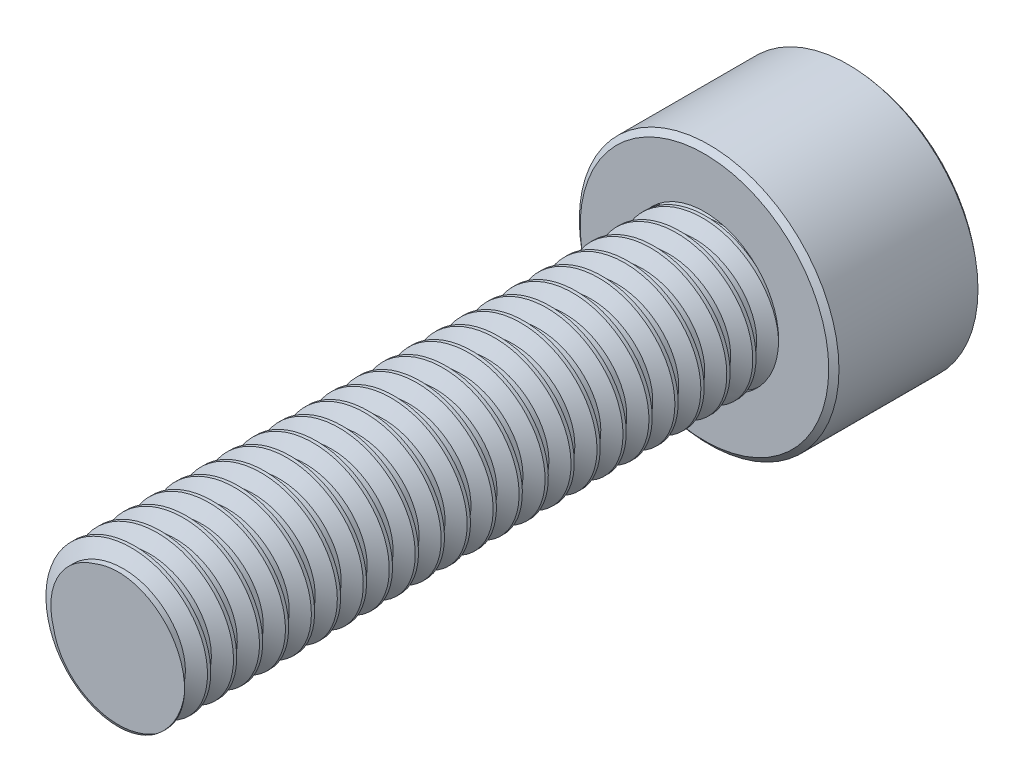
SolidWorks part; units mm, degrees
ref_plane "Front Plane" through (0, 0, 0) normal (0, 0, 1) x (1, 0, 0)
ref_plane "Top Plane" through (0, 0, 0) normal (0, 1, 0) x (1, 0, 0)
ref_plane "Right Plane" through (0, 0, 0) normal (1, 0, 0) x (0, 0, -1)
sketch "Sketch3" plane through (0, 0, 0) normal (0, 0, 1) x (1, 0, 0)
  circle A0 centre (0, 0) radius 2
extrude "Boss-Extrude2" add sketch "Sketch3" along normal blind 16
sketch "Sketch4" plane through (0, 0, 0) normal (0, 0, -1) x (-1, 0, 0)
  circle A0 centre (0, 0) radius 3.5
extrude "Boss-Extrude3" add sketch "Sketch4" along normal blind 4
sketch "Sketch5" plane through (0, 0, -4) normal (0, 0, -1) x (-1, 0, 0)
  circle A0 centre (0, 0) radius 3.35
extrude "Cut-Extrude1" cut sketch "Sketch5" against normal blind 4 draft 50 flip side to cut
sketch "Sketch6" plane through (0, 0, 0) normal (0, 0, 1) x (1, 0, 0)
  circle A0 centre (0, 0) radius 3.35
extrude "Cut-Extrude2" cut sketch "Sketch6" against normal blind 4 draft 50 flip side to cut
thread "Thread1" pitch 0.7 method cut profile "Thread Profile1" start angle 0, offset 3.3, length 20, pitch 0.7, diameter 4
ref_plane "Plane1" through (2, 0, -0.7) normal (0, -1, 0) x (1, 0, 0)
sketch "Thread Profile1" plane through (2, 0, -0.7) normal (0, -1, 0) x (1, 0, 0)
  line L0 (0, 0) -> (0, 0.7) construction
  line L11 (0, 0) -> (0, 0.6125)
  line L12 (0, 0.6125) -> (-0.3789, 0.3937)
  line L13 (-0.3789, 0.3937) -> (-0.3789, 0.2187)
  line L15 (-0.3789, 0.2187) -> (0, 0)
  line L17 (-0.3789, 0.3062) -> (0, 0.3062) construction
  point P2 (0, 0)
  dimension "Pitch" = 0.7
  dimension "Profile_Angle" = 60
  dimension "Profile_Land" = 0.175
  dimension "Profile_Height" = 0.3789
sketch "Sketch12" plane through (0, 0, -4) normal (0, 0, -1) x (-1, 0, 0)
  line L1 (-1.074, -1.0471) -> (0.3698, -1.4537)
  line L2 (0.3698, -1.4537) -> (1.4439, -0.4066)
  line L3 (1.4439, -0.4066) -> (1.074, 1.0471)
  line L4 (1.074, 1.0471) -> (-0.3698, 1.4537)
  line L5 (-0.3698, 1.4537) -> (-1.4439, 0.4066)
  line L6 (-1.4439, 0.4066) -> (-1.074, -1.0471)
  circle A0 centre (0, 0) radius 1.299 construction
  dimension "D1" = 3
extrude "Cut-Extrude3" cut sketch "Sketch12" against normal blind 2.8
fillet "Fillet2" radius 0.1 12 edges at (0.3698, 1.4537, -2.6) (0.3521, -1.2504, -1.2) (1.2589, -0.3203, -1.2) (-0.9068, -0.9301, -1.2) (-1.2589, 0.3203, -1.2) (-0.3521, 1.2504, -1.2) (0.9068, 0.9301, -1.2) (1.4439, 0.4066, -2.6) (1.074, -1.0471, -2.6) (-1.4439, -0.4066, -2.6) (-0.3698, -1.4537, -2.6) (-1.074, 1.0471, -2.6)
fillet "Fillet3" radius 0.1 12 edges at (0.366, 1.4387, -4) (-0.3521, 1.2504, -4) (-1.0629, 1.0363, -4) (-1.2589, 0.3203, -4) (-1.429, -0.4024, -4) (-0.9068, -0.9301, -4) (-0.366, -1.4387, -4) (0.3521, -1.2504, -4) (1.0629, -1.0363, -4) (1.2589, -0.3203, -4) (1.429, 0.4024, -4) (0.9068, 0.9301, -4)
